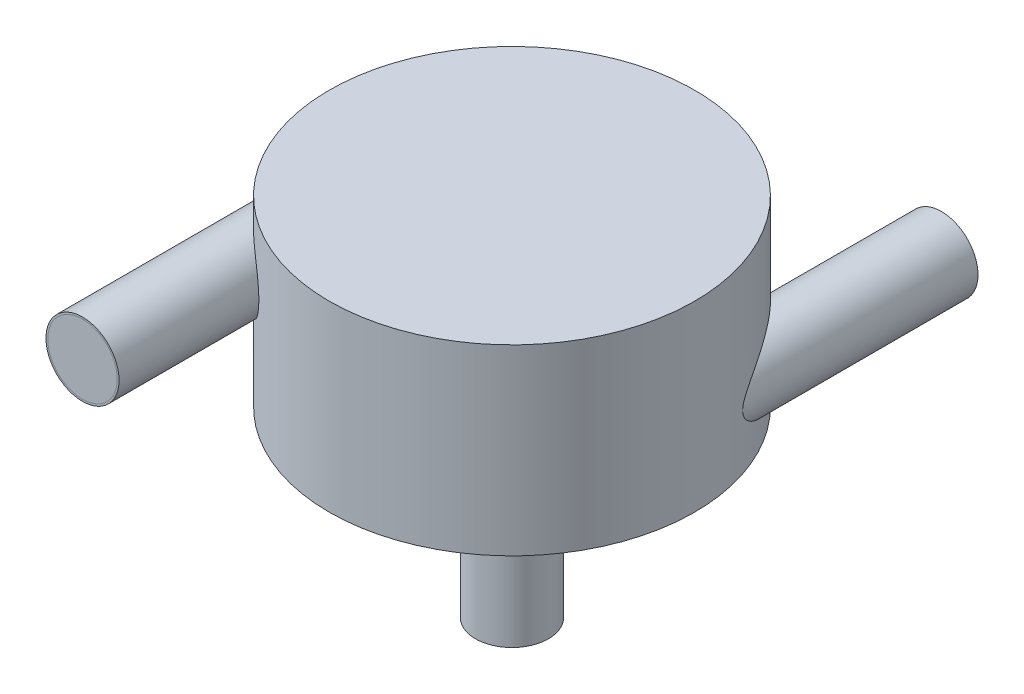
SolidWorks part; units mm, degrees
ref_plane "Front Plane"
ref_plane "Top Plane" through (0, 0, 0) normal (0, 1, 0) x (1, 0, 0)
ref_plane "Right Plane" through (0, 0, 0) normal (1, 0, 0) x (0, 0, -1)
sketch "Sketch1" plane through (0, 0, 0) normal (0, 1, 0) x (1, 0, 0)
  circle A0 centre (0, 0) radius 1000
  dimension "D1" = 2000
extrude "Boss-Extrude1" add sketch "Sketch1" along normal blind 1000
ref_plane "Inlet 1 Plane" through (0, 0, 1600) normal (0, 0, 1) x (1, 0, 0)
ref_plane "Inlet 2 Plane" through (0, 0, -1600) normal (0, 0, 1) x (1, 0, 0)
sketch "Sketch3" plane through (0, 0, 0) normal (0, -1, 0) x (1, 0, 0)
  circle A0 centre (0, 0) radius 200
  dimension "D1" = 400
extrude "Outlet Extrude" add sketch "Sketch3" along normal blind 1000
sketch "Sketch2" plane through (0, 0, 1600) normal (0, 0, 1) x (1, 0, 0)
  line L0 (-200, -1000) -> (200, -1000) construction
  circle A0 centre (-750, 650) radius 200
  dimension "D1" = 400
  dimension "D2" = 750
  dimension "D3" = 1650
extrude "Inlet 1" add sketch "Sketch2" against normal up to surface up to face at (0, 1000, 1000)
sketch "Sketch4" plane through (0, 0, -1600) normal (0, 0, 1) x (1, 0, 0)
  line L0 (-200, -1000) -> (200, -1000) construction
  circle A0 centre (750, 300) radius 200
  dimension "D3" = 400
  dimension "D1" = 1300
  dimension "D2" = 750
extrude "Inlet 2" add sketch "Sketch4" against normal up to surface
shell "Shell1" thickness 10
sketch "Sketch5" plane through (0, 0, 1600) normal (0, 0, 1) x (1, 0, 0)
  circle A0 centre (-750, 650) radius 190 construction
  circle A1 centre (-750, 650) radius 190
extrude "Lid 1" add sketch "Sketch5" against normal blind 50 separate body
sketch "Sketch6" plane through (0, 0, -1600) normal (0, 0, -1) x (-1, 0, 0)
  circle A0 centre (-750, 300) radius 190 construction
  circle A3 centre (-750, 300) radius 190
extrude "Lid 2" add sketch "Sketch6" against normal blind 50 separate body
sketch "Sketch7" plane through (0, -1000, 0) normal (0, -1, 0) x (1, 0, 0)
  circle A0 centre (0, 0) radius 190 construction
  circle A1 centre (0, 0) radius 190
extrude "Lid 3" add sketch "Sketch7" against normal blind 50 separate body
